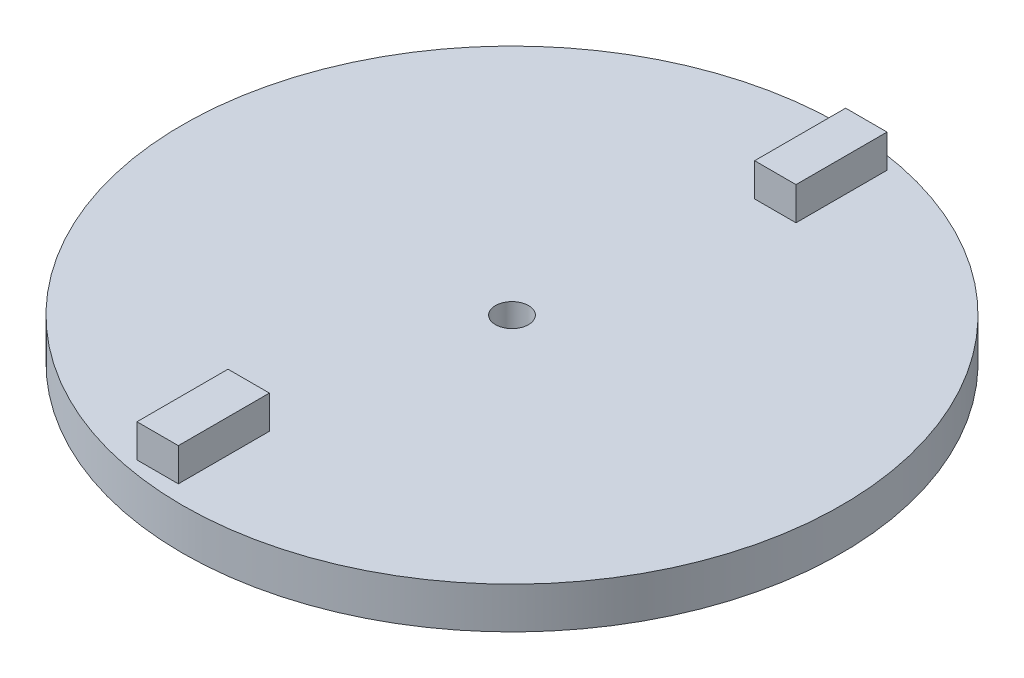
SolidWorks part; units mm, degrees
ref_plane "Front Plane" through (0, 0, 0) normal (0, 0, 1) x (1, 0, 0)
ref_plane "Top Plane" through (0, 0, 0) normal (0, 1, 0) x (1, 0, 0)
ref_plane "Right Plane" through (0, 0, 0) normal (1, 0, 0) x (0, 0, -1)
sketch "Sketch1" plane through (0, 0, 0) normal (0, 1, 0) x (1, 0, 0)
  line L5 (-6.322, 12.6439) -> (6.322, -12.6439) construction
  line L6 (-6.322, -12.6439) -> (6.322, 12.6439) construction
  circle A0 centre (0, 0) radius 50.5758
  circle A1 centre (0, 0) radius 2.54
  dimension "D1" = 5.08
extrude "Boss-Extrude1" add sketch "Sketch1" along normal blind 6.35
sketch "Sketch2" plane through (0, 0, 0) normal (1, 0, 0) x (0, 0, -1)
  line L0 (0, 6.35) -> (-40.4084, 6.35)
  line L1 (50.5758, 6.35) -> (-50.5758, 6.35) construction
  line L3 (-40.4084, 6.35) -> (-48.0284, 6.35)
  line L4 (-40.4084, 6.35) -> (-40.4084, 11.43)
  line L5 (-40.4084, 11.43) -> (-48.0284, 11.43)
  line L6 (-48.0284, 6.35) -> (-48.0284, 11.43)
  line L7 (-40.4084, 6.35) -> (-34.0584, 6.35)
  line L8 (-40.4084, 6.35) -> (-40.4084, 11.43)
  line L9 (-40.4084, 11.43) -> (-34.0584, 11.43)
  line L10 (-34.0584, 6.35) -> (-34.0584, 11.43)
  dimension "D1" = 40.4084
  dimension "D2" = 5.08
  dimension "D3" = 7.62
  dimension "D4" = 6.35
extrude "Boss-Extrude3" add sketch "Sketch2" against normal blind 9.525 contours L6 L3 L4 L5 | L0 L10 L9 L4 region at (0, 8.89, 37.2334) region at (0, 8.89, 44.2184)
sketch "Sketch3" plane through (0, 0, 0) normal (1, 0, 0) x (0, 0, -1)
  line L1 (-48.0284, 6.35) -> (-34.0584, 6.35)
  line L2 (-48.0284, 6.35) -> (-48.0284, 11.43)
  line L3 (-48.0284, 11.43) -> (-34.0584, 11.43)
  line L4 (-34.0584, 6.35) -> (-34.0584, 11.43)
extrude "Cut-Extrude1" cut sketch "Sketch3" against normal blind 3.175
pattern_circular "CirPattern2" count 2 every 180 about axis through (0, 6.35, 0) along (0, 1, 0) of "Boss-Extrude3"
sketch "Sketch4" plane through (0, 0, 0) normal (-1, 0, 0) x (0, 0, 1)
  line L1 (-48.0284, 11.43) -> (-34.0584, 11.43)
  line L2 (-48.0284, 11.43) -> (-48.0284, 6.35)
  line L3 (-48.0284, 6.35) -> (-34.0584, 6.35)
  line L4 (-34.0584, 11.43) -> (-34.0584, 6.35)
extrude "Cut-Extrude2" cut sketch "Sketch4" against normal blind 3.175
